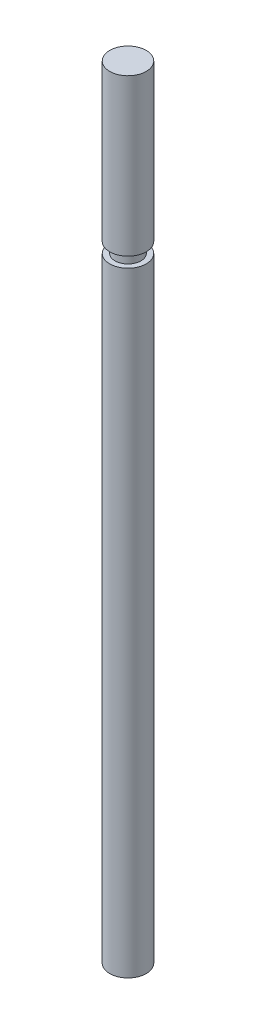
SolidWorks part; units mm, degrees
ref_plane "Front Plane" through (0, 0, 0) normal (0, 0, 1) x (1, 0, 0)
ref_plane "Top Plane" through (0, 0, 0) normal (0, 1, 0) x (1, 0, 0)
ref_plane "Right Plane" through (0, 0, 0) normal (1, 0, 0) x (0, 0, -1)
sketch "Sketch1" plane through (0, 0, 0) normal (0, 1, 0) x (1, 0, 0)
  circle A0 centre (0, 0) radius 1.75
  dimension "D1" = 3.5
extrude "Boss-Extrude1" add sketch "Sketch1" along normal blind 75
ref_plane "Plane1" through (0, 60, 0) normal (0, 1, 0) x (1, 0, 0)
sketch "Sketch2" plane through (0, 60, 0) normal (0, 1, 0) x (1, 0, 0)
  circle A0 centre (0, 0) radius 1.75 construction
  circle A1 centre (0, 0) radius 1.75
  circle A2 centre (0, 0) radius 1.25
  dimension "D1" = 0.5
extrude "Cut-Extrude1" cut sketch "Sketch2" against normal blind 1 contours A1 A2 region at (-1.7005, 60, 0)
